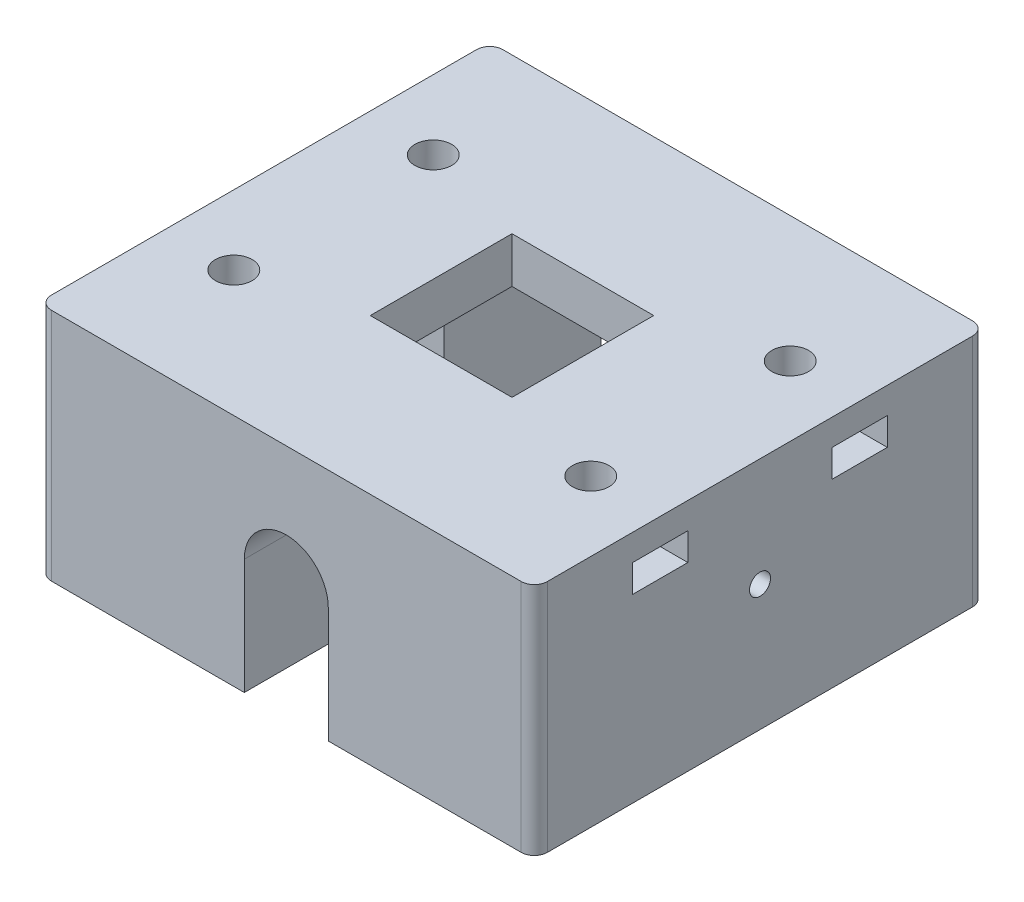
SolidWorks part; units mm, degrees
note: The reader was unsure of these and kept them because the rebuilt part matched: shared geometry of "Sketch2<3>".
ref_plane "Front Plane" through (0, 0, 0) normal (0, 0, 1) x (1, 0, 0)
ref_plane "Top Plane" through (0, 0, 0) normal (0, 1, 0) x (1, 0, 0)
ref_plane "Right Plane" through (0, 0, 0) normal (1, 0, 0) x (0, 0, -1)
sketch "Sketch1" plane through (0, 0, 0) normal (0, 1, 0) x (1, 0, 0)
  line L4 (-12.5, 12.5) -> (-12.5, -12.5)
  line L5 (-33.5, 12.5) -> (33.5, 12.5)
  line L6 (-33.5, 12.5) -> (-33.5, -12.5)
  line L7 (-33.5, -12.5) -> (33.5, -12.5)
  line L8 (33.5, 12.5) -> (33.5, -12.5)
  line L9 (0, -12.5) -> (0, 12.5) construction
  line L10 (-33.5, 0) -> (33.5, 0) construction
  line L11 (12.5, 12.5) -> (12.5, -12.5)
  line L12 (-25, 12.5) -> (-25, 20.5)
  line L13 (-25, 20.5) -> (25, 20.5)
  line L14 (25, 20.5) -> (25, 12.5)
  point P0 (0, 0)
  point P13 (0, 20.5)
  dimension "D1" = 25
  dimension "D2" = 21
  dimension "D3" = 21
  dimension "D4" = 67
  dimension "D5" = 50
  dimension "D6" = 8
sketch "Sketch2" plane through (0, 0, 0) normal (0, 1, 0) x (1, 0, 0)
  line L0 (-33.75, 13) -> (-26, 13)
  line L1 (-26, 13) -> (-26, 43)
  line L2 (-26, 43) -> (-47.25, 43)
  line L3 (-47.25, 43) -> (-47.25, -43)
  line L4 (-47.25, -43) -> (47.25, -43)
  line L5 (47.25, -43) -> (47.25, 43)
  line L6 (47.25, 43) -> (26, 43)
  line L7 (26, 43) -> (26, 13)
  line L8 (26, 13) -> (33.75, 13)
  line L9 (33.75, 13) -> (33.75, -13)
  line L11 (-33.75, -13) -> (-33.75, 13)
  line L12 (-33.5, 12.5) -> (33.5, 12.5) construction
  line L13 (-33.5, 12.5) -> (-33.5, -12.5) construction
  line L14 (-33.5, -12.5) -> (33.5, -12.5) construction
  line L15 (33.5, 12.5) -> (33.5, -12.5) construction
  line L16 (25, 20.5) -> (25, 12.5) construction
  line L17 (-25, 12.5) -> (-25, 20.5) construction
  line L18 (0, -18.15) -> (0, 18.15) construction
  line L19 (-42.125, 3.125) -> (-38.875, 3.125)
  line L20 (-42.125, 3.125) -> (-42.125, -3.125)
  line L21 (-42.125, -3.125) -> (-38.875, -3.125)
  line L22 (-38.875, 3.125) -> (-38.875, -3.125)
  line L23 (-40.5, -3.125) -> (-40.5, 3.125) construction
  line L24 (-42.125, 0) -> (-38.875, 0) construction
  line L25 (42.125, 0) -> (38.875, 0) construction
  line L26 (40.5, -3.125) -> (40.5, 3.125) construction
  line L27 (38.875, 3.125) -> (38.875, -3.125)
  line L28 (42.125, -3.125) -> (38.875, -3.125)
  line L29 (42.125, 3.125) -> (42.125, -3.125)
  line L30 (42.125, 3.125) -> (38.875, 3.125)
  line L31 (-15, -12.5) -> (-15, -14.5)
  line L32 (-15, -14.5) -> (15, -14.5)
  line L33 (15, -14.5) -> (15, -12.5)
  line L34 (0, -12.5) -> (0, 12.5) construction
  line L35 (-33.75, -13) -> (-15.75, -13)
  line L36 (-15.75, -13) -> (-15.75, -15)
  line L37 (-15.75, -15) -> (15.75, -15)
  line L38 (15.75, -15) -> (15.75, -13)
  line L39 (15.75, -13) -> (33.75, -13)
  point P13 (-47.25, 0)
  point P25 (-40.5, 0)
  point P39 (40.5, 0)
  point P44 (0, -14.5)
  dimension "D1" = 0.5
  dimension "D2" = 0.25
  dimension "D3" = 0.5
  dimension "D4" = 0.25
  dimension "D5" = 0.5
  dimension "D6" = 1
  dimension "D7" = 1
  dimension "D8" = 13.5
  dimension "D9" = 0.75
  dimension "D10" = 30
  dimension "D11" = 3.25
  dimension "D12" = 6.25
  dimension "D13" = 6.75
  dimension "D14" = 30
  dimension "D15" = 2
  dimension "D16" = 0.5
  dimension "D17" = 0.5
  dimension "D18" = 30
extrude "Boss-Extrude1" add sketch "Sketch2" along normal blind 36
sketch "Sketch4" plane through (47.25, 0, 0) normal (1, 0, 0) x (0, 0, -1)
  line L0 (-43, 36) -> (43, 36) construction
  point P0 (0, 24)
  dimension "D1" = 12
hole_wizard "M3 Clearance Hole1" positions "Sketch4" profile "Sketch5" hole size "M3" standard "ISO" end condition through all
sketch "Sketch5" plane through (47.25, 24, 0) normal (0, 1, 0) x (0, 0, -1)
  line L0 (0, 0) -> (0, 94.5)
  line L1 (0, 94.5) -> (2, 94.5)
  line L2 (2, 94.5) -> (2, 0)
  line L5 (2, 0) -> (0, 0)
  line L11 (0, -6.35) -> (0, 107.95) construction
  dimension "Thru Hole Dia." = 4
  dimension "Thru Hole Depth" = 94.5
sketch "Sketch6" plane through (0, 36, 0) normal (0, 1, 0) x (1, 0, 0)
  line L0 (-47.25, 43) -> (47.25, 43)
  line L1 (47.25, 43) -> (47.25, -43)
  line L2 (47.25, -43) -> (-47.25, -43)
  line L3 (-47.25, -43) -> (-47.25, 43)
  line L4 (-33.5, 0) -> (33.5, 0) construction
  line L5 (-13.5, 13.5) -> (13.5, 13.5)
  line L6 (-13.5, 13.5) -> (-13.5, -13.5)
  line L7 (-13.5, -13.5) -> (13.5, -13.5)
  line L8 (13.5, 13.5) -> (13.5, -13.5)
  line L9 (0, -13.5) -> (0, 13.5) construction
  line L10 (-13.5, 0) -> (13.5, 0) construction
  line L11 (-33.5, 12.5) -> (33.5, 12.5) construction
  line L12 (-12.5, 12.5) -> (-12.5, -12.5) construction
  point P4 (0, 0)
  dimension "D1" = 1
  dimension "D2" = 1
extrude "Boss-Extrude2" add sketch "Sketch6" along normal blind 8.7
fillet "Fillet1" radius 2.5 4 edges at (-47.25, 22.35, -43) (-47.25, 22.35, 43) (47.25, 22.35, 43) (47.25, 22.35, -43)
extrude "Cut-Extrude1" cut sketch "Sketch2<3>" along normal blind 27 contours L29 L30 L27 L28 | L39 L38 L37 L36 L35 L11 L0 L1 L2 L3 L4 L5 L6 L7 L8 L9 L30 L29 L28 L27 L19 L22 L21 L20
sketch "Sketch2<3>" plane through (0, 0, 0) normal (0, 1, 0) x (1, 0, 0) same geometry as "Sketch2"
sketch "Sketch8" plane through (0, 0, 43) normal (0, 0, 1) x (1, 0, 0)
  line L1 (-8, 22) -> (-8, 0)
  line L2 (-25, 0) -> (25, 0) construction
  line L3 (8, 22) -> (8, 0)
  line L4 (8, 0) -> (-8, 0)
  arc A0 (8, 22) -> (-8, 22) centre (0, 22) ccw
  dimension "D1" = 16
  dimension "D2" = 22
extrude "Cut-Extrude2" cut sketch "Sketch8" against normal through all
sketch "Sketch10" plane through (0, 44.7, 0) normal (0, 1, 0) x (1, 0, 0)
  line L2 (0, -18.15) -> (0, 18.15) construction
  line L3 (-36.85, 0) -> (36.85, 0) construction
  line L4 (0, -12.5) -> (0, 12.5) construction
  line L5 (-33.5, 0) -> (33.5, 0) construction
  point P0 (-34, 19)
  point P8 (34, 19)
  point P12 (34, -19)
  point P13 (-34, -19)
  dimension "D1" = 34
  dimension "D2" = 19
hole_wizard "M6 Clearance Hole1" positions "Sketch10" profile "Sketch11" hole size "M6" standard "ISO" end condition through all
sketch "Sketch11" plane through (-34, 44.7, -19) normal (1, 0, 0) x (0, 0, 1)
  line L0 (0, 0) -> (0, 44.7)
  line L1 (0, 44.7) -> (3.5, 44.7)
  line L2 (3.5, 44.7) -> (3.5, 0)
  line L5 (3.5, 0) -> (0, 0)
  line L11 (0, -6.35) -> (0, 107.95) construction
  dimension "Thru Hole Dia." = 7
  dimension "Thru Hole Depth" = 44.7
sketch "Sketch9" plane through (0, 0, -43) normal (0, 0, -1) x (-1, 0, 0)
  line L0 (-44.75, 44.7) -> (44.75, 44.7) construction
  line L1 (-29.375, 41.2) -> (-23.125, 41.2)
  line L2 (-29.375, 41.2) -> (-29.375, 37.95)
  line L3 (-29.375, 37.95) -> (-23.125, 37.95)
  line L4 (-23.125, 41.2) -> (-23.125, 37.95)
  line L5 (-26.25, 37.95) -> (-26.25, 41.2) construction
  line L6 (-29.375, 39.575) -> (-23.125, 39.575) construction
  line L7 (0, 18.15) -> (0, -18.15) construction
  line L8 (29.375, 39.575) -> (23.125, 39.575) construction
  line L9 (26.25, 37.95) -> (26.25, 41.2) construction
  line L10 (23.125, 41.2) -> (23.125, 37.95)
  line L11 (29.375, 37.95) -> (23.125, 37.95)
  line L12 (29.375, 41.2) -> (29.375, 37.95)
  line L13 (29.375, 41.2) -> (23.125, 41.2)
  line L14 (-47.25, 0) -> (-47.25, 44.7) construction
  point P0 (-26.25, 39.575)
  point P17 (26.25, 39.575)
  dimension "D1" = 3.25
  dimension "D2" = 6.25
  dimension "D3" = 21
  dimension "D4" = 3.5
sketch "Sketch12" plane through (47.25, 0, 0) normal (1, 0, 0) x (0, 0, -1)
  line L1 (-24.25, 39.7) -> (-13.75, 39.7)
  line L2 (-24.25, 39.7) -> (-24.25, 34.45)
  line L3 (-24.25, 34.45) -> (-13.75, 34.45)
  line L4 (-13.75, 39.7) -> (-13.75, 34.45)
  line L5 (-19, 34.45) -> (-19, 39.7) construction
  line L6 (-24.25, 37.075) -> (-13.75, 37.075) construction
  line L7 (-40.5, 44.7) -> (40.5, 44.7) construction
  line L8 (0, 36.85) -> (0, -36.85) construction
  line L9 (24.25, 37.075) -> (13.75, 37.075) construction
  line L10 (19, 34.45) -> (19, 39.7) construction
  line L11 (13.75, 39.7) -> (13.75, 34.45)
  line L12 (24.25, 34.45) -> (13.75, 34.45)
  line L13 (24.25, 39.7) -> (24.25, 34.45)
  line L14 (24.25, 39.7) -> (13.75, 39.7)
  circle A0 centre (0, 24) radius 2 construction
  point P0 (-19, 37.075)
  point P18 (19, 37.075)
  dimension "D1" = 10.5
  dimension "D2" = 5.25
  dimension "D3" = 19
  dimension "D4" = 5
extrude "Cut-Extrude4" cut sketch "Sketch12" against normal blind 22
mirror "Mirror2" about plane through (0, 0, 0) normal (1, 0, 0) of "Cut-Extrude4"
